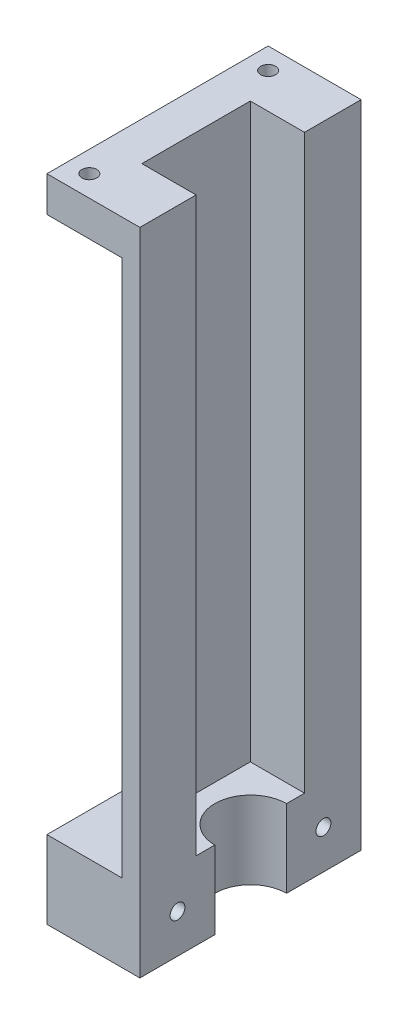
SolidWorks part; units mm, degrees
ref_plane "Front Plane" through (0, 0, 0) normal (0, 0, 1) x (1, 0, 0)
ref_plane "Top Plane" through (0, 0, 0) normal (0, 1, 0) x (1, 0, 0)
ref_plane "Right Plane" through (0, 0, 0) normal (1, 0, 0) x (0, 0, -1)
sketch "Sketch1" plane through (0, 0, 0) normal (0, 1, 0) x (1, 0, 0)
  line L0 (0, 15.6284) -> (-2.5, 15.6284)
  line L1 (-7.675, 7.625) -> (0, 7.625)
  line L2 (-7.675, 7.625) -> (-7.675, -7.725)
  line L3 (-7.675, -7.725) -> (0, -7.725)
  line L5 (-2.5, 15.6284) -> (-13.1534, 4.975)
  line L6 (0, 0) -> (-13.1534, 0) construction
  line L7 (-13.1534, -5.025) -> (-2.5, -15.6784)
  line L8 (0, -15.6784) -> (-2.5, -15.6784)
  line L9 (-13.1534, 4.975) -> (-13.1534, -5.025)
  line L10 (0, 15.6284) -> (0, 7.625)
  line L11 (0, -15.6784) -> (0, -7.725)
  line L12 (-18.1284, 0) -> (-28.3722, 0) construction
  dimension "D1" = 15.35
  dimension "D2" = 7.675
  dimension "D3" = 2.5
  dimension "D4" = 45
  dimension "D5" = 2
  dimension "D6" = 45
  dimension "D7" = 2.5
  dimension "D8" = 10
  dimension "D9" = 7.675
extrude "Boss-Extrude1" add sketch "Sketch1" along normal blind 92 contours L5 L9 L7 L8 L11 L3 L2 L1 L10 L0
sketch "Sketch2" plane through (0, 0, 0) normal (0, -1, 0) x (1, 0, 0)
  line L0 (0, 7.725) -> (0, 5.075)
  line L1 (0, 7.725) -> (-7.675, 7.725)
  line L2 (-7.675, 7.725) -> (-7.675, -7.625)
  line L3 (-7.675, -7.625) -> (0, -7.625)
  line L4 (0, -7.625) -> (0, -5.075)
  arc A0 (0, 5.075) -> (0, -5.075) centre (0, 0) ccw
  dimension "D1" = 10.15
extrude "Boss-Extrude2" add sketch "Sketch2" against normal blind 11
sketch "Sketch3" plane through (0, 92, 0) normal (0, 1, 0) x (1, 0, 0)
  line L0 (-2.5, 15.6284) -> (-13.1534, 15.6284)
  line L1 (-13.1534, 4.975) -> (-13.1534, 15.6284)
  line L2 (-2.5, -15.6784) -> (-13.1534, -15.6784)
  line L3 (-13.1534, -5.025) -> (-13.1534, -15.6784)
  line L4 (-2.5, 15.6284) -> (-13.1534, 4.975)
  line L5 (-13.1534, -5.025) -> (-2.5, -15.6784)
extrude "Boss-Extrude3" add sketch "Sketch3" against normal blind 5
sketch "Sketch4" plane through (0, 87, 0) normal (0, -1, 0) x (1, 0, 0)
  line L0 (-13.1534, 15.6784) -> (-2.5, 15.6784) construction
  line L1 (-13.1534, 5.025) -> (-13.1534, 15.6784) construction
  line L2 (-2.5, -15.6284) -> (-13.1534, -15.6284) construction
  line L3 (-13.1534, -15.6284) -> (-13.1534, -4.975) construction
  line L4 (0, -15.6284) -> (0, -7.625) construction
  circle A0 centre (-10.1534, 12.6784) radius 1.05
  circle A1 centre (-10.1534, -12.6284) radius 1.05
  dimension "D1" = 2.1
  dimension "D2" = 2.1
  dimension "D3" = 3
  dimension "D4" = 3
  dimension "D5" = 3
  dimension "D6" = 3
  dimension "D7" = 25.3069
  dimension "D8" = 10.1534
extrude "Cut-Extrude1" cut sketch "Sketch4" against normal up to next
sketch "Sketch5" plane through (0, 0, 0) normal (0, -1, 0) x (1, 0, 0)
  line L0 (-2.5, 15.6784) -> (-13.1534, 15.6784)
  line L1 (-13.1534, 15.6784) -> (-13.1534, 5.025)
  line L2 (-13.1534, 5.025) -> (-2.5, 15.6784)
  line L3 (-13.1534, -4.975) -> (-13.1534, -15.6284)
  line L4 (-13.1534, -15.6284) -> (-2.5, -15.6284)
  line L5 (-2.5, -15.6284) -> (-13.1534, -4.975)
extrude "Boss-Extrude4" add sketch "Sketch5" against normal blind 11
sketch "Sketch6" plane through (-13.1534, 0, 0) normal (-1, 0, 0) x (0, 0, 1)
  line L0 (-10.3017, 11) -> (-10.3017, 0) construction
  line L1 (11.5641, 7.6) -> (9.1393, 7.6)
  line L2 (9.1393, 7.6) -> (7.9268, 5.5)
  line L3 (7.9268, 5.5) -> (9.1393, 3.4)
  line L4 (9.1393, 3.4) -> (11.5641, 3.4)
  line L5 (11.5641, 3.4) -> (12.7766, 5.5)
  line L6 (12.7766, 5.5) -> (11.5641, 7.6)
  line L7 (-7.8768, 5.5) -> (-9.0893, 7.6)
  line L8 (-9.0893, 7.6) -> (-11.5141, 7.6)
  line L9 (-11.5141, 7.6) -> (-12.7266, 5.5)
  line L10 (-12.7266, 5.5) -> (-11.5141, 3.4)
  line L11 (-11.5141, 3.4) -> (-9.0893, 3.4)
  line L12 (-9.0893, 3.4) -> (-7.8768, 5.5)
  line L13 (-4.975, 11) -> (-15.6284, 11) construction
  line L14 (-15.6284, 0) -> (15.6784, 0) construction
  line L15 (10.3517, 11) -> (10.3517, 0) construction
  line L16 (15.6784, 11) -> (5.025, 11) construction
  line L18 (-4.975, 5.5) -> (-15.6284, 5.5) construction
  line L19 (-4.975, 87) -> (-4.975, 11) construction
  line L20 (-15.6284, 87) -> (-15.6284, 11) construction
  line L21 (15.6784, 5.5) -> (5.025, 5.5) construction
  line L22 (15.6784, 87) -> (15.6784, 11) construction
  line L23 (5.025, 87) -> (5.025, 11) construction
  circle A2 centre (10.3517, 5.5) radius 2.1 construction
  circle A3 centre (-10.3017, 5.5) radius 2.1 construction
  dimension "D1" = 4.2
  dimension "D2" = 4.2
extrude "Cut-Extrude2" cut sketch "Sketch6" against normal offset from surface (6.1534 mm away) 7 up to face at (0, 34.3333, -9.4428)
sketch "Sketch7" plane through (-13.1534, 0, 0) normal (-1, 0, 0) x (0, 0, 1)
  circle A0 centre (-10.3017, 5.5) radius 1.05
  circle A1 centre (10.3517, 5.5) radius 1.05
  dimension "D1" = 2.1
  dimension "D2" = 2.1
extrude "Cut-Extrude3" cut sketch "Sketch7" against normal up to next
chamfer "Chamfer2" distance 2 angle 45 2 edges at (-7, 5.5, 9.3017) (-7, 5.5, -11.3517)
